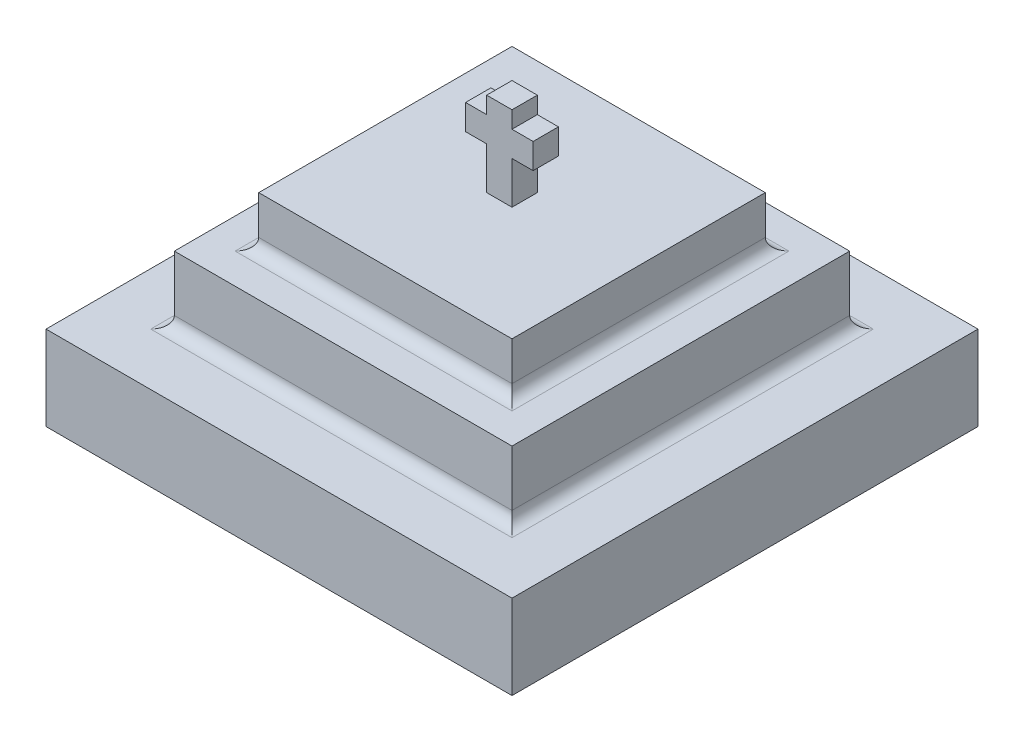
SolidWorks part; units mm, degrees
ref_plane "Front Plane" through (0, 0, 0) normal (0, 0, 1) x (1, 0, 0)
ref_plane "Top Plane" through (0, 0, 0) normal (0, 1, 0) x (1, 0, 0)
ref_plane "Right Plane" through (0, 0, 0) normal (1, 0, 0) x (0, 0, -1)
sketch "Szkic1" plane through (0, 0, 0) normal (0, 1, 0) x (1, 0, 0)
  line L1 (0, 0) -> (27.6, 0)
  line L2 (0, 0) -> (0, 27.6)
  line L3 (0, 27.6) -> (27.6, 27.6)
  line L4 (27.6, 0) -> (27.6, 27.6)
  dimension "D1" = 27.6
  dimension "D2" = 27.6
extrude "Dodanie-wyciągnięcie1" add sketch "Szkic1" along normal blind 5
sketch "Szkic2" plane through (0, 5, 0) normal (0, 1, 0) x (1, 0, 0)
  line L0 (0, 27.6) -> (0, 0) construction
  line L1 (3.8, 3.8) -> (23.8, 3.8)
  line L2 (3.8, 3.8) -> (3.8, 23.8)
  line L3 (3.8, 23.8) -> (23.8, 23.8)
  line L4 (23.8, 3.8) -> (23.8, 23.8)
  line L5 (0, 0) -> (27.6, 0) construction
  dimension "D1" = 20
  dimension "D2" = 20
  dimension "D3" = 3.8
  dimension "D4" = 3.8
extrude "Dodanie-wyciągnięcie2" add sketch "Szkic2" along normal blind 4
sketch "Szkic3" plane through (0, 9, 0) normal (0, 1, 0) x (1, 0, 0)
  line L0 (3.8, 23.8) -> (3.8, 3.8) construction
  line L1 (6.3, 6.3) -> (21.3, 6.3)
  line L2 (6.3, 6.3) -> (6.3, 21.3)
  line L3 (6.3, 21.3) -> (21.3, 21.3)
  line L4 (21.3, 6.3) -> (21.3, 21.3)
  line L5 (3.8, 3.8) -> (23.8, 3.8) construction
  dimension "D1" = 15
  dimension "D2" = 15
  dimension "D3" = 2.5
  dimension "D4" = 2.5
extrude "Dodanie-wyciągnięcie3" add sketch "Szkic3" along normal blind 3
sketch "Szkic4" plane through (0, 12, 0) normal (0, 1, 0) x (1, 0, 0)
  line L0 (6.3, 21.3) -> (6.3, 6.3) construction
  line L2 (6.3, 6.3) -> (21.3, 6.3) construction
  line L3 (13.05, 14.55) -> (14.55, 14.55)
  line L4 (13.05, 14.55) -> (13.05, 13.05)
  line L5 (13.05, 13.05) -> (14.55, 13.05)
  line L6 (14.55, 14.55) -> (14.55, 13.05)
  line L7 (13.05, 14.55) -> (14.55, 13.05) construction
  line L8 (13.05, 13.05) -> (14.55, 14.55) construction
  point P0 (13.8, 13.8)
  dimension "D1" = 1.5
  dimension "D2" = 1.5
  dimension "D3" = 7.5
  dimension "D4" = 6.75
extrude "Dodanie-wyciągnięcie4" add sketch "Szkic4" along normal blind 5
ref_plane "Płaszczyzna1" through (13.8, 0, 0) normal (1, 0, 0) x (0, 0, -1)
sketch "Szkic5" plane through (13.8, 0, 0) normal (1, 0, 0) x (0, 0, -1)
  line L1 (13.05, 17) -> (13.05, 12) construction
  line L2 (13.05, 14.5) -> (14.55, 14.5)
  line L3 (14.55, 17) -> (14.55, 12) construction
  line L4 (14.55, 14.5) -> (14.55, 16)
  line L5 (14.55, 16) -> (13.05, 16)
  line L6 (13.05, 16) -> (13.05, 14.5)
  dimension "D2" = 1.5
extrude "Dodanie-wyciągnięcie5" add sketch "Szkic5" along normal blind 2 and the other way blind 2 contours L5 L6 L2 L4
fillet "Zaokrąglenie1" radius 0.7 8 edges at (13.8, 9, -21.3) (21.3, 9, -13.8) (6.3, 9, -13.8) (13.8, 9, -6.3) (13.8, 5, -23.8) (23.8, 5, -13.8) (13.8, 5, -3.8) (3.8, 5, -13.8)
shell "Skorupa1" thickness 1 removed face at (13.8, 0, -13.8)
sketch "Szkic7" plane through (1, 0, 0) normal (1, 0, 0) x (0, 0, -1)
  line L0 (23.8, 2.3836) -> (23.8, 1.7)
  line L1 (23.8, 1.7) -> (3.8, 1.7)
  line L2 (3.8, 1.7) -> (3.8, 2.3836)
  line L3 (3.8, 2.3836) -> (23.8, 2.3836)
  line L4 (27.6, 5) -> (27.6, 0) construction
  line L6 (0, 0) -> (27.6, 0) construction
  dimension "D1" = 3.8
  dimension "D2" = 20
  dimension "D3" = 1.7
extrude "Dodanie-wyciągnięcie6" add sketch "Szkic7" along normal blind 0.4 draft 26
ref_plane "Płaszczyzna2" through (0, 0, -13.8) normal (0, 0, 1) x (1, 0, 0)
ref_axis "Oś2" through (13.8, -0.85, -13.8) along (0, 1, 0)
pattern_circular "Szyk kołowy3" count 4 over 360 about axis through (13.8, -0.85, -13.8) along (0, 1, 0) of "Dodanie-wyciągnięcie6"
